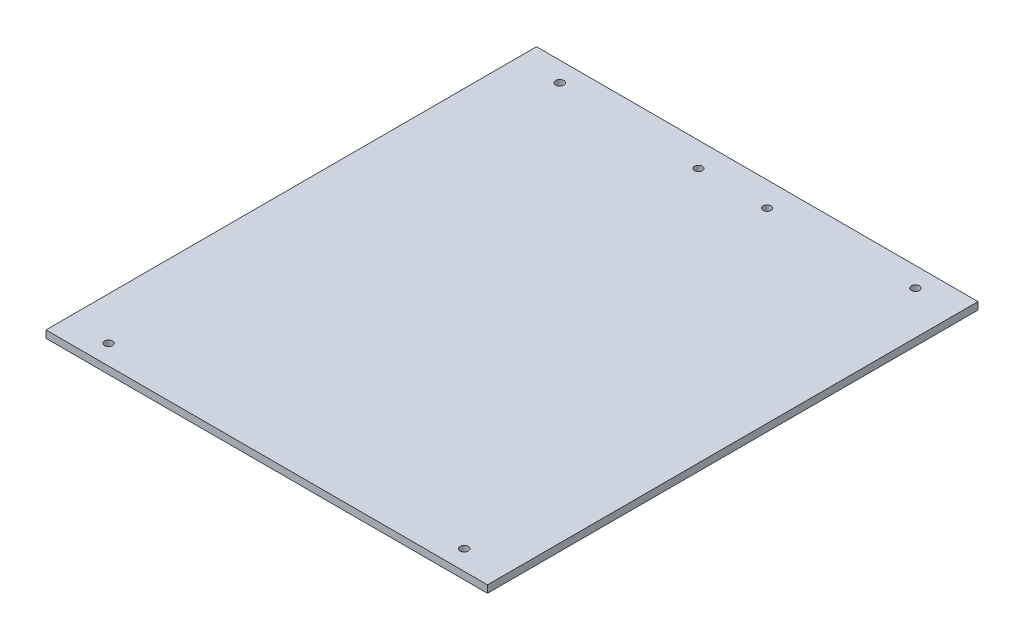
SolidWorks part; units mm, degrees
ref_plane "Front Plane" through (0, 0, 0) normal (0, 0, 1) x (1, 0, 0)
ref_plane "Top Plane" through (0, 0, 0) normal (0, 1, 0) x (1, 0, 0)
ref_plane "Right Plane" through (0, 0, 0) normal (1, 0, 0) x (0, 0, -1)
sketch "Sketch1" plane through (0, 0, 0) normal (0, 1, 0) x (1, 0, 0)
  line L1 (-90, 100) -> (90, 100)
  line L2 (-90, 100) -> (-90, -100)
  line L3 (-90, -100) -> (90, -100)
  line L4 (90, 100) -> (90, -100)
  line L5 (-90, 100) -> (90, -100) construction
  line L6 (-90, -100) -> (90, 100) construction
  point P0 (0, 0)
  dimension "D1" = 180
  dimension "D2" = 200
extrude "Boss-Extrude1" add sketch "Sketch1" along normal blind 3
sketch "Sketch2" plane through (0, 3, 0) normal (0, 1, 0) x (1, 0, 0)
  line L0 (90, -100) -> (90, 100) construction
  line L1 (90, 100) -> (-90, 100) construction
  line L2 (0, 110.5785) -> (0, -114.1459) construction
  line L3 (-112.1444, 0) -> (117.8654, 0) construction
  circle A0 centre (72.5, 92) radius 1.65
  circle A1 centre (-72.5, 92) radius 1.65
  circle A2 centre (-72.5, -92) radius 1.65
  circle A3 centre (72.5, -92) radius 1.65
  dimension "D1" = 3.3
  dimension "D2" = 17.5
  dimension "D3" = 8
extrude "Cut-Extrude1" cut sketch "Sketch2" against normal through all
sketch "Sketch3" plane through (0, 3, 0) normal (0, 1, 0) x (1, 0, 0)
  line L0 (0, 117.3388) -> (0, -121.3792) construction
  line L1 (90, 100) -> (-90, 100) construction
  circle A0 centre (14, 90) radius 1.6
  circle A1 centre (-14, 90) radius 1.6
  dimension "D1" = 3.2
  dimension "D2" = 14
  dimension "D3" = 10
extrude "Cut-Extrude2" cut sketch "Sketch3" against normal through all
